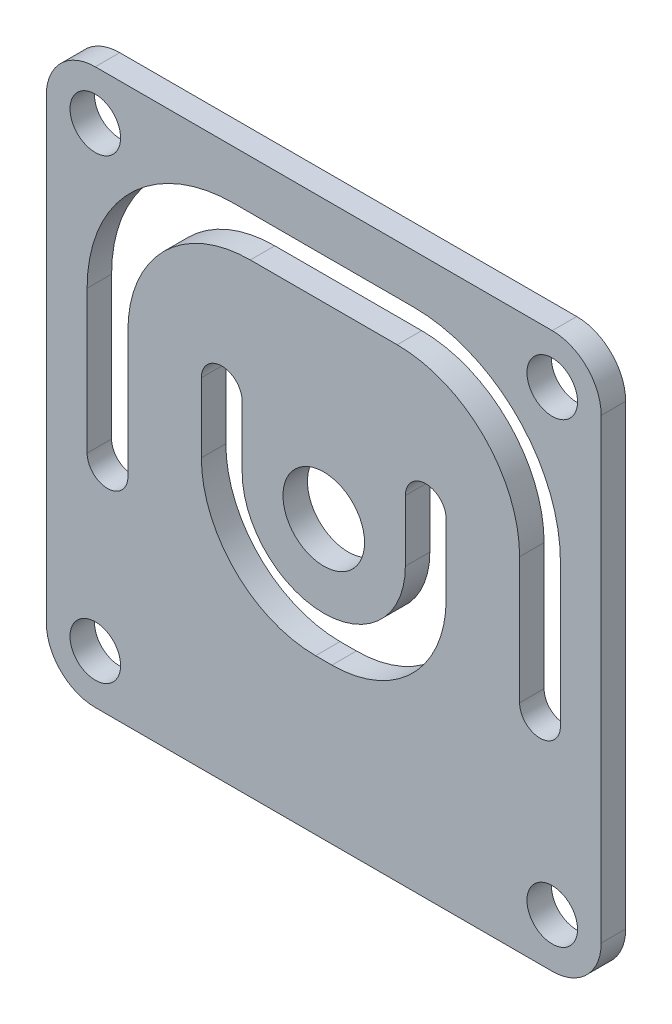
SolidWorks part; units mm, degrees
ref_plane "正面" through (0, 0, 0) normal (0, 0, 1) x (1, 0, 0)
ref_plane "平面" through (0, 0, 0) normal (0, 1, 0) x (1, 0, 0)
ref_plane "右側面" through (0, 0, 0) normal (1, 0, 0) x (0, 0, -1)
sketch "ｽｹｯﾁ1" plane through (0, 0, 0) normal (0, 0, 1) x (1, 0, 0)
  line L1 (0, 0) -> (34, 0)
  line L2 (0, 0) -> (0, 34)
  line L3 (0, 34) -> (34, 34)
  line L4 (34, 0) -> (34, 34)
  dimension "D1" = 34
  dimension "D2" = 34
extrude "ﾎﾞｽ - 押し出し1" add sketch "ｽｹｯﾁ1" along normal blind 1.5
sketch "ｽｹｯﾁ2" plane through (0, 0, 1.5) normal (0, 0, 1) x (1, 0, 0)
  line L0 (17, 34) -> (17, 0) construction
  line L1 (34, 34) -> (0, 34) construction
  line L2 (0, 0) -> (34, 0) construction
  line L3 (0, 17) -> (34, 17) construction
  line L4 (0, 34) -> (0, 0) construction
  line L5 (34, 0) -> (34, 34) construction
  line L7 (3, 31) -> (31, 31) construction
  line L8 (3, 31) -> (3, 3) construction
  line L9 (3, 3) -> (31, 3) construction
  line L10 (31, 31) -> (31, 3) construction
  circle A0 centre (17, 17) radius 2.5
  circle A1 centre (3, 31) radius 1.55
  circle A2 centre (31, 31) radius 1.55
  circle A3 centre (3, 3) radius 1.55
  circle A4 centre (31, 3) radius 1.55
  point P18 (31, 17)
  point P19 (17, 31)
  dimension "D1" = 5
  dimension "D4" = 3.1
  dimension "D5" = 3.1
  dimension "D6" = 3.1
  dimension "D7" = 3.1
  dimension "D2" = 28
  dimension "D3" = 28
extrude "ｶｯﾄ - 押し出し1" cut sketch "ｽｹｯﾁ2" against normal through all
sketch "ｽｹｯﾁ3" plane through (0, 0, 1.5) normal (0, 0, 1) x (1, 0, 0)
  line L0 (0, 17) -> (34, 17) construction
  line L1 (0, 34) -> (0, 0) construction
  line L2 (34, 0) -> (34, 34) construction
  line L3 (17, 34) -> (17, 0) construction
  line L4 (34, 34) -> (0, 34) construction
  line L5 (0, 0) -> (34, 0) construction
  line L6 (2.5, 12) -> (5, 12)
  line L7 (5, 12) -> (5, 21)
  line L8 (12.5, 28.5) -> (17, 28.5)
  line L9 (17, 28.5) -> (17, 31)
  line L10 (17, 31) -> (11.5, 31)
  line L11 (2.5, 22) -> (2.5, 12)
  arc A0 (12.5, 28.5) -> (5, 21) centre (12.5, 21) ccw
  arc A1 (11.5, 31) -> (2.5, 22) centre (11.5, 22) ccw
  circle A2 centre (3.75, 13.25) radius 1.25
  dimension "D6" = 7.5
  dimension "D7" = 9
  dimension "D1" = 2.5
  dimension "D2" = 2.5
  dimension "D3" = 5
  dimension "D4" = 3
  dimension "D5" = 2.5
extrude "ｶｯﾄ - 押し出し2" cut sketch "ｽｹｯﾁ3" against normal through all contours A2 L7 A0 L8 L9 L10 A1 L11 | A2 region at (3.75, 13.25, 1.5) region at (2.7292, 17.625, 1.5)
mirror "ﾐﾗｰ1" about plane through (17, 0, 0) normal (1, 0, 0) of "ｶｯﾄ - 押し出し2"
sketch "ｽｹｯﾁ4" plane through (0, 0, 1.5) normal (0, 0, 1) x (1, 0, 0)
  line L0 (12, 17) -> (12, 22)
  line L1 (12, 22) -> (9.5, 22)
  line L2 (17, 34) -> (17, 0) construction
  line L3 (34, 34) -> (0, 34) construction
  line L4 (0, 0) -> (34, 0) construction
  line L5 (9.5, 22) -> (9.5, 16.5)
  line L6 (16.5, 9.5) -> (17, 9.5)
  line L7 (17, 9.5) -> (17, 12)
  circle A0 centre (17, 17) radius 5
  arc A1 (16.5, 9.5) -> (9.5, 16.5) centre (16.5, 16.5) cw
  dimension "D1" = 10
  dimension "D5" = 7
  dimension "D2" = 2.5
  dimension "D3" = 5
  dimension "D4" = 7.5
extrude "ｶｯﾄ - 押し出し3" cut sketch "ｽｹｯﾁ4" against normal through all contours A1 L6 L7 A0 L0 L1 L5 region at (12.2079, 15.0415, 1.5)
fillet "ﾌｨﾚｯﾄ1" radius 1.25 2 edges at (12, 22, 0.75) (9.5, 22, 0.75)
mirror "ﾐﾗｰ3" about plane through (17, 0, 0) normal (1, 0, 0) of "ﾌｨﾚｯﾄ1", "ｶｯﾄ - 押し出し3"
fillet "ﾌｨﾚｯﾄ2" radius 3 4 edges at (0, 0, 0.75) (34, 0, 0.75) (34, 34, 0.75) (0, 34, 0.75)
